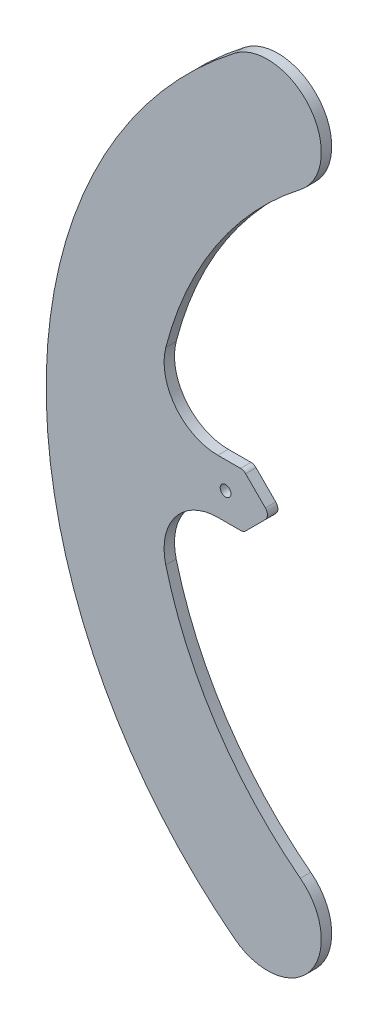
SolidWorks part; units mm, degrees
ref_plane "Front Plane" through (0, 0, 0) normal (0, 0, 1) x (1, 0, 0)
ref_plane "Top Plane" through (0, 0, 0) normal (0, 1, 0) x (1, 0, 0)
ref_plane "Right Plane" through (0, 0, 0) normal (1, 0, 0) x (0, 0, -1)
sketch "Sketch1" plane through (0, 0, 0) normal (0, 0, 1) x (1, 0, 0)
  line L0 (-32.8019, 0) -> (18.2589, 0) construction
  line L1 (70.5, 105) -> (70.5, 135) construction
  line L2 (205.5, -110) -> (-64.5, -110)
  line L3 (205.5, -110) -> (205.5, 110)
  line L4 (205.5, 110) -> (-64.5, 110)
  line L5 (-19.5, 6.5) -> (-19.5, -6.5)
  line L6 (-18.5, -7.5) -> (-9.5, -7.5)
  line L7 (-9.5, -7.5) -> (-2, 0)
  line L9 (-9.5, 7.5) -> (-18.5, 7.5)
  line L10 (-19.5, 6.5) -> (-19.5, -6.5)
  line L11 (-18.5, -7.5) -> (-9.5, -7.5)
  line L15 (-64.5, -110) -> (-64.5, 110)
  line L16 (205.5, -110) -> (-64.5, 110) construction
  line L17 (205.5, 110) -> (-64.5, -110) construction
  line L18 (-18, 7.5) -> (-34.2318, 7.5)
  line L19 (-18.5, -7.5) -> (-34.2318, -7.5)
  line L146 (-9.5, 7.5) -> (-18.5, 7.5)
  line L162 (-9.5, -7.5) -> (-2, 0)
  line L169 (-2, 0) -> (-9.5, 7.5)
  line L170 (-2, 0) -> (-9.5, 7.5)
  circle A0 centre (-14.5, 0) radius 1.5 construction
  arc A2 (-19.5, -6.5) -> (-18.5, -7.5) centre (-18.5, -6.5) ccw
  circle A6 centre (-14.5, 0) radius 1.5
  circle A7 centre (-14.5, 0) radius 1.5
  circle A8 centre (70.5, 0) radius 135
  circle A9 centre (70.5, 0) radius 105
  circle A11 centre (-2.8144, 95) radius 15
  circle A12 centre (-2.8144, -95) radius 15
  arc A32 (-19.5, -6.5) -> (-18.5, -7.5) centre (-18.5, -6.5) ccw
  arc A65 (-18.5, 7.5) -> (-19.5, 6.5) centre (-18.5, 6.5) ccw
  arc A66 (-18.5, 7.5) -> (-19.5, 6.5) centre (-18.5, 6.5) ccw
  point P19 (-64.5, 0)
  point P27 (70.5, 110)
  dimension "D3" = 270
  dimension "D5" = 30
  dimension "D2" = 55
  dimension "D4" = 220
  dimension "D1" = 0
extrude "Boss-Extrude1" add sketch "Sketch1" along normal blind 2.9 contours A11 | A8 A12 A9 A11 | A12 | L18 A9 L19 L10 | L146 L10 L11 L162 L170 A6 region at (-2.8144, -95, 0) region at (-37.1858, 0, 0) region at (-2.8144, 95, 0) region at (-26.9408, 0, 0) region at (-12.3671, 0, 0)
fillet "Fillet1" radius 15 2 edges at (-34.2318, -7.5, 1.45) (-34.2318, 7.5, 1.45)
fillet "Fillet2" radius 2 3 edges at (-9.5, -7.5, 1.45) (-9.5, 7.5, 1.45) (-2, 0, 1.45)
